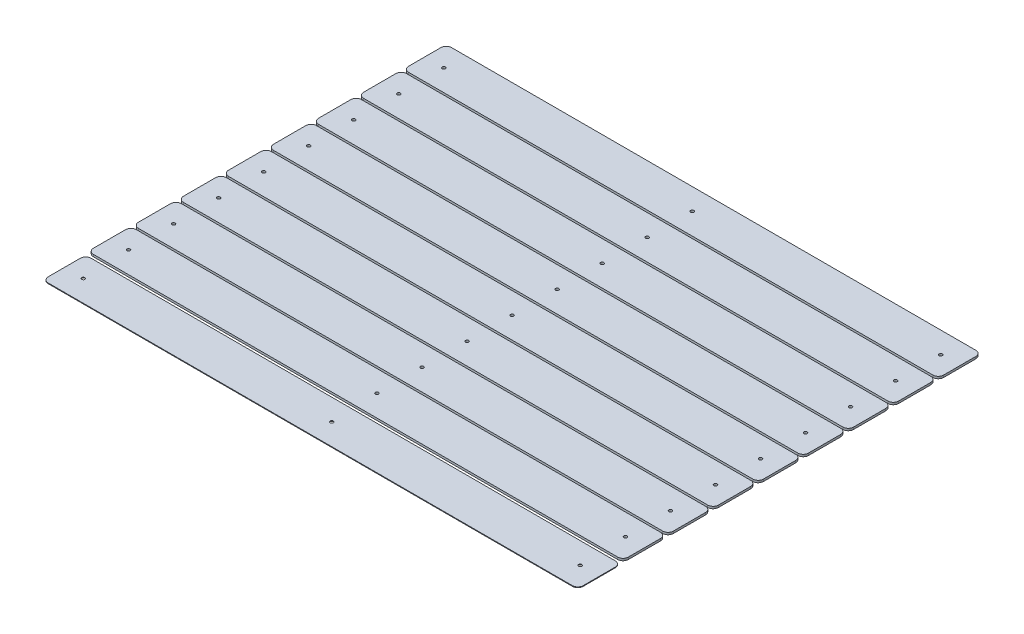
SolidWorks part; units mm, degrees
ref_plane "Front Plane" through (0, 0, 0) normal (0, 0, 1) x (1, 0, 0)
ref_plane "Top Plane" through (0, 0, 0) normal (0, 1, 0) x (1, 0, 0)
ref_plane "Right Plane" through (0, 0, 0) normal (1, 0, 0) x (0, 0, -1)
sketch "Sketch1" plane through (0, 0, 0) normal (0, 1, 0) x (1, 0, 0)
  line L1 (-316.7761, -25.4) -> (316.7761, -25.4)
  line L2 (-316.7761, -25.4) -> (-316.7761, 25.4)
  line L3 (-316.7761, 25.4) -> (316.7761, 25.4)
  line L4 (316.7761, -25.4) -> (316.7761, 25.4)
  line L5 (-316.7761, -25.4) -> (316.7761, 25.4) construction
  line L6 (-316.7761, 25.4) -> (316.7761, -25.4) construction
  point P0 (0, 0)
  dimension "D1" = 50.8
  dimension "D2" = 633.5522
extrude "Boss-Extrude1" add sketch "Sketch1" along normal blind 0.7937
fillet "Fillet1" radius 6.35 4 edges at (-316.7761, 0.3969, -25.4) (-316.7761, 0.3969, 25.4) (316.7761, 0.3969, -25.4) (316.7761, 0.3969, 25.4)
hole_wizard "#6 Clearance Hole1" positions "Sketch2" profile "Sketch3" hole size "#6" standard "ANSI Inch" end condition through all
sketch "Sketch2" plane through (0, 0.7937, 0) normal (0, 1, 0) x (1, 0, 0)
  line L0 (-316.7761, 0) -> (316.7761, 0) construction
  line L1 (-316.7761, 19.05) -> (-316.7761, -19.05) construction
  line L2 (316.7761, -19.05) -> (316.7761, 19.05) construction
  point P8 (0, 0)
  point P12 (-294.2568, 0)
  point P14 (294.2568, 0)
  dimension "D1" = 294.2568
  dimension "D2" = 294.2568
sketch "Sketch3" plane through (294.2568, 0.7937, 0) normal (1, 0, 0) x (0, 0, 1)
  line L0 (0, 0) -> (0, 0.7937)
  line L1 (0, 0.7937) -> (1.8986, 0.7937)
  line L2 (1.8986, 0.7937) -> (1.8986, 0)
  line L5 (1.8986, 0) -> (0, 0)
  line L11 (0, -6.35) -> (0, 107.95) construction
  dimension "Thru Hole Dia." = 3.7973
  dimension "Thru Hole Depth" = 0.7937
sketch "Sketch4" plane through (0, 0.7937, 0) normal (0, 1, 0) x (1, 0, 0)
  line L4 (316.7761, 34.5028) -> (316.7761, 72.6028)
  line L5 (-310.4261, 28.1528) -> (310.4261, 28.1528)
  line L6 (-316.7761, 72.6028) -> (-316.7761, 34.5028)
  line L7 (310.4261, 78.9528) -> (-310.4261, 78.9528)
  line L8 (316.7761, 87.8428) -> (316.7761, 125.9428)
  line L9 (-310.4261, 81.4928) -> (310.4261, 81.4928)
  line L10 (-316.7761, 125.9428) -> (-316.7761, 87.8428)
  line L11 (310.4261, 132.2928) -> (-310.4261, 132.2928)
  line L12 (316.7761, 141.1828) -> (316.7761, 179.2828)
  line L13 (-310.4261, 134.8328) -> (310.4261, 134.8328)
  line L14 (-316.7761, 179.2828) -> (-316.7761, 141.1828)
  line L15 (310.4261, 185.6328) -> (-310.4261, 185.6328)
  line L16 (316.7761, 194.5228) -> (316.7761, 232.6228)
  line L17 (-310.4261, 188.1728) -> (310.4261, 188.1728)
  line L18 (-316.7761, 232.6228) -> (-316.7761, 194.5228)
  line L19 (310.4261, 238.9728) -> (-310.4261, 238.9728)
  line L20 (316.7761, 247.8628) -> (316.7761, 285.9628)
  line L21 (-310.4261, 241.5128) -> (310.4261, 241.5128)
  line L22 (-316.7761, 285.9628) -> (-316.7761, 247.8628)
  line L23 (310.4261, 292.3128) -> (-310.4261, 292.3128)
  line L24 (316.7761, 301.2028) -> (316.7761, 339.3028)
  line L25 (-310.4261, 294.8528) -> (310.4261, 294.8528)
  line L26 (-316.7761, 339.3028) -> (-316.7761, 301.2028)
  line L27 (310.4261, 345.6528) -> (-310.4261, 345.6528)
  line L28 (316.7761, 354.5428) -> (316.7761, 392.6428)
  line L29 (-310.4261, 348.1928) -> (310.4261, 348.1928)
  line L30 (-316.7761, 392.6428) -> (-316.7761, 354.5428)
  line L31 (310.4261, 398.9928) -> (-310.4261, 398.9928)
  line L32 (316.7761, 407.8828) -> (316.7761, 445.9828)
  line L33 (-310.4261, 401.5328) -> (310.4261, 401.5328)
  line L34 (-316.7761, 445.9828) -> (-316.7761, 407.8828)
  line L35 (310.4261, 452.3328) -> (-310.4261, 452.3328)
  arc A7 (310.4261, 28.1528) -> (316.7761, 34.5028) centre (310.4261, 34.5028) ccw
  arc A8 (316.7761, 72.6028) -> (310.4261, 78.9528) centre (310.4261, 72.6028) ccw
  circle A9 centre (294.2568, 53.5528) radius 1.8987
  circle A10 centre (0, 53.5528) radius 1.8987
  circle A11 centre (-294.2568, 53.5528) radius 1.8987
  arc A12 (-316.7761, 34.5028) -> (-310.4261, 28.1528) centre (-310.4261, 34.5028) ccw
  arc A13 (-310.4261, 78.9528) -> (-316.7761, 72.6028) centre (-310.4261, 72.6028) ccw
  arc A14 (310.4261, 81.4928) -> (316.7761, 87.8428) centre (310.4261, 87.8428) ccw
  arc A15 (316.7761, 125.9428) -> (310.4261, 132.2928) centre (310.4261, 125.9428) ccw
  circle A16 centre (294.2568, 106.8928) radius 1.8987
  circle A17 centre (0, 106.8928) radius 1.8987
  circle A18 centre (-294.2568, 106.8928) radius 1.8987
  arc A19 (-316.7761, 87.8428) -> (-310.4261, 81.4928) centre (-310.4261, 87.8428) ccw
  arc A20 (-310.4261, 132.2928) -> (-316.7761, 125.9428) centre (-310.4261, 125.9428) ccw
  arc A21 (310.4261, 134.8328) -> (316.7761, 141.1828) centre (310.4261, 141.1828) ccw
  arc A22 (316.7761, 179.2828) -> (310.4261, 185.6328) centre (310.4261, 179.2828) ccw
  circle A23 centre (294.2568, 160.2328) radius 1.8987
  circle A24 centre (0, 160.2328) radius 1.8987
  circle A25 centre (-294.2568, 160.2328) radius 1.8987
  arc A26 (-316.7761, 141.1828) -> (-310.4261, 134.8328) centre (-310.4261, 141.1828) ccw
  arc A27 (-310.4261, 185.6328) -> (-316.7761, 179.2828) centre (-310.4261, 179.2828) ccw
  arc A28 (310.4261, 188.1728) -> (316.7761, 194.5228) centre (310.4261, 194.5228) ccw
  arc A29 (316.7761, 232.6228) -> (310.4261, 238.9728) centre (310.4261, 232.6228) ccw
  circle A30 centre (294.2568, 213.5728) radius 1.8987
  circle A31 centre (0, 213.5728) radius 1.8987
  circle A32 centre (-294.2568, 213.5728) radius 1.8987
  arc A33 (-316.7761, 194.5228) -> (-310.4261, 188.1728) centre (-310.4261, 194.5228) ccw
  arc A34 (-310.4261, 238.9728) -> (-316.7761, 232.6228) centre (-310.4261, 232.6228) ccw
  arc A35 (310.4261, 241.5128) -> (316.7761, 247.8628) centre (310.4261, 247.8628) ccw
  arc A36 (316.7761, 285.9628) -> (310.4261, 292.3128) centre (310.4261, 285.9628) ccw
  circle A37 centre (294.2568, 266.9128) radius 1.8986
  circle A38 centre (0, 266.9128) radius 1.8986
  circle A39 centre (-294.2568, 266.9128) radius 1.8986
  arc A40 (-316.7761, 247.8628) -> (-310.4261, 241.5128) centre (-310.4261, 247.8628) ccw
  arc A41 (-310.4261, 292.3128) -> (-316.7761, 285.9628) centre (-310.4261, 285.9628) ccw
  arc A42 (310.4261, 294.8528) -> (316.7761, 301.2028) centre (310.4261, 301.2028) ccw
  arc A43 (316.7761, 339.3028) -> (310.4261, 345.6528) centre (310.4261, 339.3028) ccw
  circle A44 centre (294.2568, 320.2528) radius 1.8987
  circle A45 centre (0, 320.2528) radius 1.8987
  circle A46 centre (-294.2568, 320.2528) radius 1.8987
  arc A47 (-316.7761, 301.2028) -> (-310.4261, 294.8528) centre (-310.4261, 301.2028) ccw
  arc A48 (-310.4261, 345.6528) -> (-316.7761, 339.3028) centre (-310.4261, 339.3028) ccw
  arc A49 (310.4261, 348.1928) -> (316.7761, 354.5428) centre (310.4261, 354.5428) ccw
  arc A50 (316.7761, 392.6428) -> (310.4261, 398.9928) centre (310.4261, 392.6428) ccw
  circle A51 centre (294.2568, 373.5928) radius 1.8986
  circle A52 centre (0, 373.5928) radius 1.8986
  circle A53 centre (-294.2568, 373.5928) radius 1.8986
  arc A54 (-316.7761, 354.5428) -> (-310.4261, 348.1928) centre (-310.4261, 354.5428) ccw
  arc A55 (-310.4261, 398.9928) -> (-316.7761, 392.6428) centre (-310.4261, 392.6428) ccw
  arc A56 (310.4261, 401.5328) -> (316.7761, 407.8828) centre (310.4261, 407.8828) ccw
  arc A57 (316.7761, 445.9828) -> (310.4261, 452.3328) centre (310.4261, 445.9828) ccw
  circle A58 centre (294.2568, 426.9328) radius 1.8987
  circle A59 centre (0, 426.9328) radius 1.8987
  circle A60 centre (-294.2568, 426.9328) radius 1.8987
  arc A61 (-316.7761, 407.8828) -> (-310.4261, 401.5328) centre (-310.4261, 407.8828) ccw
  arc A62 (-310.4261, 452.3328) -> (-316.7761, 445.9828) centre (-310.4261, 445.9828) ccw
  dimension "D1" = 8
extrude "Boss-Extrude2" add sketch "Sketch4" along normal blind 2.54 separate body
